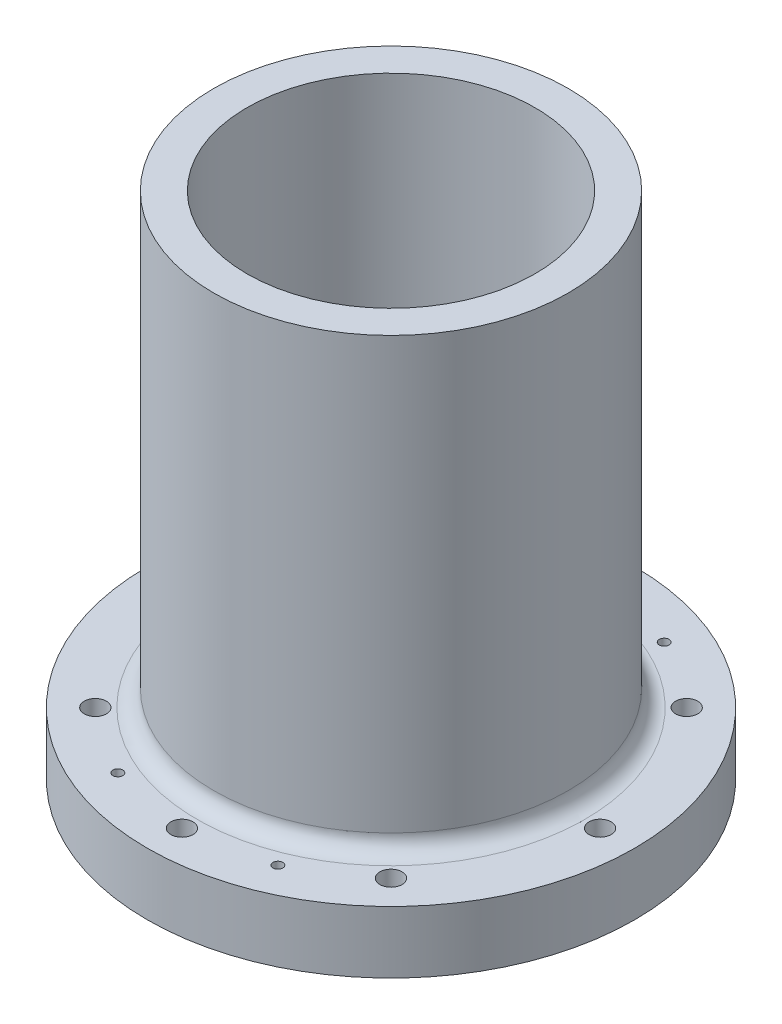
SolidWorks part; units mm, degrees
ref_plane "Front Plane" through (0, 0, 0) normal (0, 0, 1) x (1, 0, 0)
ref_plane "Top Plane" through (0, 0, 0) normal (0, 1, 0) x (1, 0, 0)
ref_plane "Right Plane" through (0, 0, 0) normal (1, 0, 0) x (0, 0, -1)
sketch "Sketch2" plane through (0, 0, 0) normal (0, 1, 0) x (1, 0, 0)
  circle A0 centre (0, 0) radius 41.275
  circle A1 centre (0, 0) radius 50.8
  dimension "D1" = 101.6
  dimension "D2" = 82.55
extrude "Base Cylinder" add sketch "Sketch2" along normal blind 292.1
sketch "Sketch3" plane through (0, 0, 0) normal (0, -1, 0) x (1, 0, 0)
  circle A0 centre (0, 0) radius 41.275
  circle A1 centre (0, 0) radius 69.85
  dimension "D1" = 139.7
extrude "Aft Flange" add sketch "Sketch3" against normal blind 17.78
sketch "Sketch4" plane through (0, 292.1, 0) normal (0, 1, 0) x (1, 0, 0)
  circle A0 centre (0, 0) radius 41.275
  circle A1 centre (0, 0) radius 69.85
extrude "Forward Flange" add sketch "Sketch4" against normal blind 17.78
sketch "Sketch6" plane through (0, 0, 0) normal (0, -1, 0) x (1, 0, 0)
  circle A0 centre (0, 0) radius 50.0761
  circle A1 centre (0, 0) radius 47.0027
  dimension "D1" = 100.1522
  dimension "D2" = 94.0054
extrude "O-Ring Slot 1" cut sketch "Sketch6" against normal blind 1.9812
sketch "Sketch7" plane through (0, 292.1, 0) normal (0, 1, 0) x (1, 0, 0)
  circle A0 centre (0, 0) radius 50.0761
  circle A1 centre (0, 0) radius 47.0027
  dimension "D1" = 100.1522
  dimension "D2" = 94.0054
extrude "O-Ring Slot 2" cut sketch "Sketch7" against normal blind 1.9812
sketch "Sketch8" plane through (0, 0, 0) normal (0, -1, 0) x (1, 0, 0)
  circle A0 centre (-59.9186, 0) radius 3.175
  circle A1 centre (-42.3688, 42.3688) radius 3.175
  circle A2 centre (0, 59.9186) radius 3.175
  circle A3 centre (42.3688, 42.3688) radius 3.175
  circle A4 centre (59.9186, 0) radius 3.175
  circle A5 centre (42.3688, -42.3688) radius 3.175
  circle A6 centre (0, -59.9186) radius 3.175
  circle A7 centre (-42.3688, -42.3688) radius 3.175
  point P36 (0, 0)
  dimension "D2" = 6.35
  dimension "D1" = 59.9186
  dimension "D3" = 8
extrude "Cut-Extrude4" cut sketch "Sketch8" against normal through all both and the other way through all
fillet "Fillet1" radius 4.7625 2 edges at (0, 17.78, -50.8) (0, 274.32, 50.8)
sketch "Sketch9" plane through (0, 292.1, 0) normal (0, 1, 0) x (1, 0, 0)
  line L0 (0, -76.2) -> (0, 76.2) construction
  line L1 (-32.6024, 78.7092) -> (32.6024, -78.7092) construction
  line L2 (-32.0538, -77.3847) -> (32.0538, 77.3847) construction
  circle A0 centre (0, 0) radius 59.9186 construction
  circle A1 centre (-22.9299, 55.3576) radius 3.175
  circle A2 centre (22.9299, -55.3576) radius 3.175
  circle A3 centre (22.9299, 55.3576) radius 3.175
  circle A4 centre (-22.9299, -55.3576) radius 3.175
  point P6 (0, 0)
  point P9 (0, 0)
  point P16 (0, 0)
  dimension "D1" = 119.8372
  dimension "D3" = 6.35
  dimension "D4" = 6.35
  dimension "D5" = 6.35
  dimension "D6" = 6.35
  dimension "D2" = 22.5
  dimension "D7" = 22.5
extrude "Cut-Extrude5" cut sketch "Sketch9" against normal blind 7.62
sketch "Sketch10" plane through (0, 0, 0) normal (0, -1, 0) x (1, 0, 0)
  line L0 (0, -76.2) -> (0, 76.2) construction
  line L1 (-33.7592, 81.5019) -> (33.7592, -81.5019) construction
  line L2 (-33.8465, -81.7128) -> (33.8465, 81.7128) construction
  circle A0 centre (0, 0) radius 59.9186 construction
  circle A1 centre (-22.9299, 55.3576) radius 3.175
  circle A2 centre (22.9299, -55.3576) radius 3.175
  circle A3 centre (22.9299, 55.3576) radius 3.175
  circle A4 centre (-22.9299, -55.3576) radius 3.175
  point P6 (0, 0)
  point P9 (0, 0)
  point P16 (0, 0)
  dimension "D1" = 119.8372
  dimension "D2" = 6.35
  dimension "D3" = 6.35
  dimension "D5" = 6.35
  dimension "D6" = 6.35
  dimension "D4" = 22.5
  dimension "D7" = 22.5
extrude "Cut-Extrude6" cut sketch "Sketch10" against normal blind 7.62
sketch "Sketch11" plane through (0, 284.48, 0) normal (0, 1, 0) x (1, 0, 0)
  circle A0 centre (-22.9299, 55.3576) radius 1.4097
  circle A1 centre (22.9299, 55.3576) radius 1.4097
  circle A2 centre (-22.9299, -55.3576) radius 1.4097
  circle A3 centre (22.9299, -55.3576) radius 1.4097
  dimension "D1" = 2.8194
  dimension "D2" = 2.8194
  dimension "D3" = 2.8194
  dimension "D4" = 2.8194
extrude "Cut-Extrude7" cut sketch "Sketch11" against normal up to next
sketch "Sketch12" plane through (0, 7.62, 0) normal (0, -1, 0) x (1, 0, 0)
  circle A0 centre (-22.9299, 55.3576) radius 1.4097
  circle A1 centre (22.9299, 55.3576) radius 1.4097
  circle A2 centre (-22.9299, -55.3576) radius 1.4097
  circle A3 centre (22.9299, -55.3576) radius 1.4097
  dimension "D1" = 2.8194
  dimension "D2" = 2.8194
  dimension "D3" = 2.8194
  dimension "D4" = 2.8194
extrude "Cut-Extrude8" cut sketch "Sketch12" against normal up to next
ref_plane "Plane1" through (-69.85, 0, 0) normal (1, 0, 0) x (0, 0, -1)
ref_plane "Plane3" through (69.85, 0, 0) normal (1, 0, 0) x (0, 0, -1)
ref_plane "Plane4" through (0, 283.21, 0) normal (0, 1, 0) x (1, 0, 0)
sketch "Sketch13" plane through (-69.85, 0, 0) normal (1, 0, 0) x (0, 0, -1)
  line L0 (76.835, 283.21) -> (-76.835, 283.21) construction
  circle A0 centre (0, 283.21) radius 2.3114
  dimension "D1" = 4.6228
extrude "Cut-Extrude10" cut sketch "Sketch13" along normal blind 6.35
sketch "Sketch14" plane through (69.85, 0, 0) normal (1, 0, 0) x (0, 0, -1)
  circle A0 centre (0, 283.21) radius 2.3114
  dimension "D1" = 4.6228
extrude "Cut-Extrude11" cut sketch "Sketch14" against normal blind 6.35
ref_axis "Axis1" through (63.5, 283.21, 0) along (1, 0, 0)
ref_axis "Axis2" through (-63.5, 283.21, 0) along (-1, 0, 0)
sketch "Sketch17" plane through (0, 0, 0) normal (0, -1, 0) x (-1, 0, 0)
  circle A0 centre (0, 0) radius 69.85
extrude "Cut-Extrude12" [suppressed] cut sketch "Sketch17" against normal blind 146.05
sketch "Sketch18" plane through (0, 292.1, 0) normal (0, 1, 0) x (1, 0, 0)
  circle A0 centre (0, 0) radius 69.85
extrude "Cut-Extrude13" cut sketch "Sketch18" against normal blind 146.05
